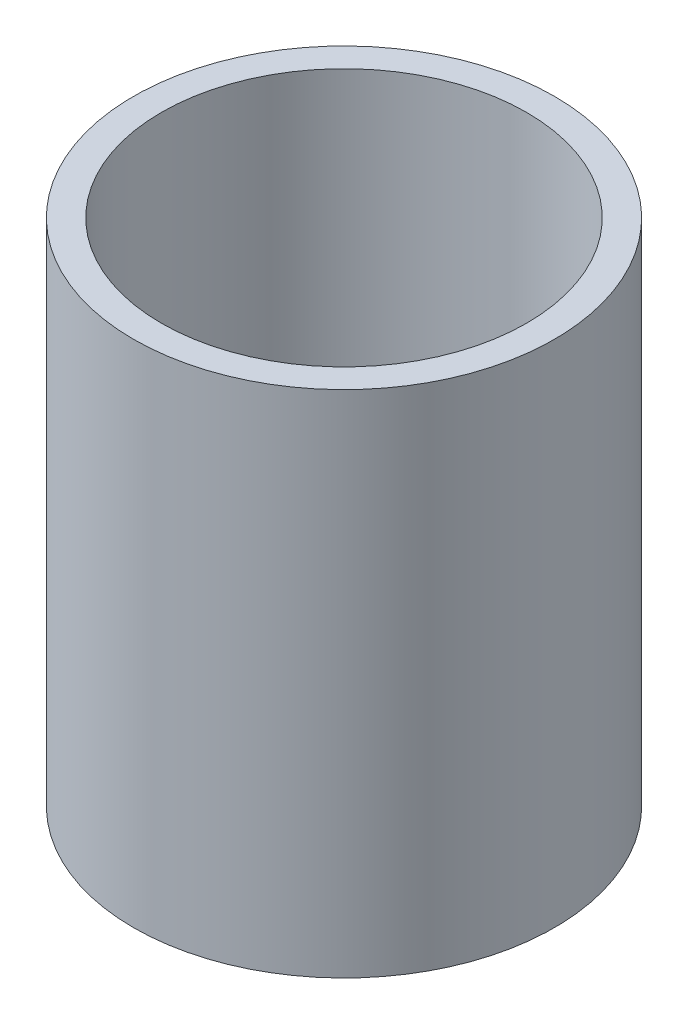
SolidWorks part; units mm, degrees
ref_plane "Front Plane" through (0, 0, 0) normal (0, 0, 1) x (1, 0, 0)
ref_plane "Top Plane" through (0, 0, 0) normal (0, 1, 0) x (1, 0, 0)
ref_plane "Right Plane" through (0, 0, 0) normal (1, 0, 0) x (0, 0, -1)
sketch "Sketch1" plane through (0, 0, 0) normal (0, 1, 0) x (1, 0, 0)
  circle A0 centre (0, 0) radius 45
  dimension "SLEEVE_OD" = 90
extrude "Boss-Extrude1" add sketch "Sketch1" along normal blind 108.9529
sketch "Sketch2" plane through (0, 0, 0) normal (0, 1, 0) x (1, 0, 0)
  circle A0 centre (0, 0) radius 39.0499
  dimension "BORE_D" = 78.0998
extrude "Cut-Extrude1" cut sketch "Sketch2" along normal through all
chamfer "Chamfer1" distance 3.5916 angle 45 rebuild error yes
